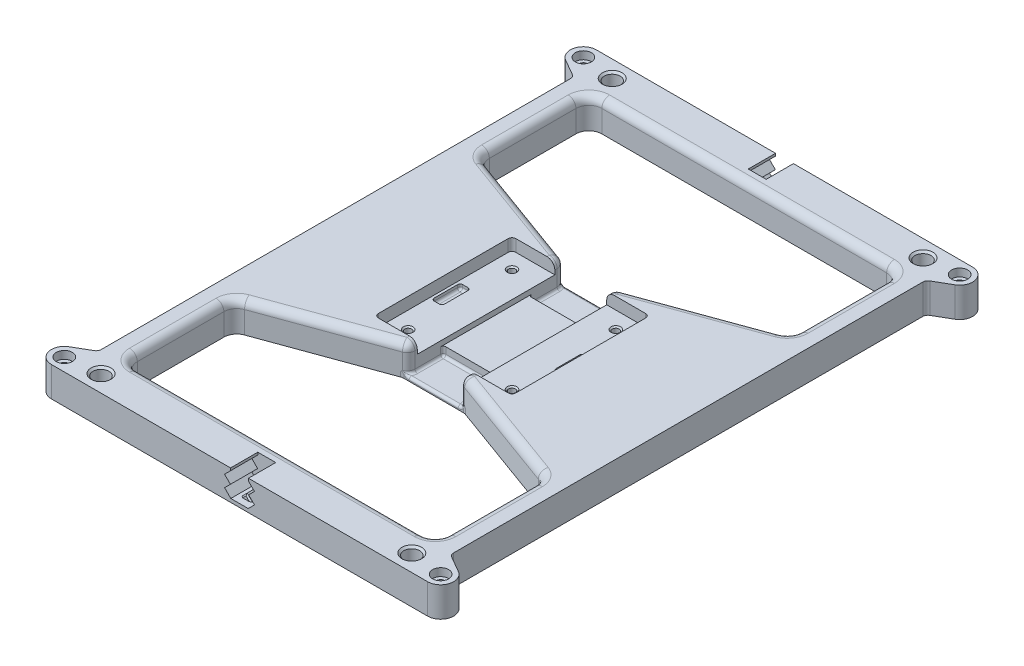
SolidWorks part; units mm, degrees
ref_plane "Front Plane" through (0, 0, 0) normal (0, 0, 1) x (1, 0, 0)
ref_plane "Top Plane" through (0, 0, 0) normal (0, 1, 0) x (1, 0, 0)
ref_plane "Right Plane" through (0, 0, 0) normal (1, 0, 0) x (0, 0, -1)
sketch "Sketch1" plane through (0, 0, 0) normal (0, 1, 0) x (1, 0, 0)
  line L0 (0, 0) -> (0, 90) construction
  line L1 (67.875, 90) -> (-67.875, 90) construction
  line L2 (-67.875, 90) -> (-67.875, 0)
  line L3 (-67.875, 0) -> (67.875, 0)
  line L4 (-67.875, 90) -> (-67.875, 103)
  line L5 (-65.875, 105) -> (65.875, 105)
  line L6 (0, 105) -> (0, 90) construction
  line L7 (67.875, 90) -> (67.875, 103)
  line L8 (67.875, 90) -> (67.875, 0)
  line L14 (-67.875, 93) -> (67.875, 93) construction
  circle A1 centre (-59.875, 98.5) radius 3.075 construction
  circle A2 centre (59.875, 98.5) radius 3.075 construction
  arc A10 (67.875, 103) -> (65.875, 105) centre (65.875, 103) ccw
  arc A11 (-67.875, 103) -> (-65.875, 105) centre (-65.875, 103) cw
  point P42 (67.875, 105)
  point P45 (-67.875, 105)
  dimension "D3" = 6.15
  dimension "D4" = 2
  dimension "D1" = 67.875
  dimension "D2" = 90
  dimension "D6" = 8
  dimension "D7" = 8.5
  dimension "D8" = 12
  dimension "D9" = 3
  dimension "D11" = 105
extrude "Boss-Extrude1" add sketch "Sketch1" along normal blind 11.5
sketch "Sketch3" plane through (0, 11.5, 0) normal (0, 1, 0) x (1, 0, 0)
  line L0 (0, 0) -> (-67.875, 0) construction
  line L2 (0, 0) -> (0, 105) construction
  line L3 (65.875, 105) -> (-65.875, 105) construction
  line L4 (3.96, -16.3) -> (3.96, 16.3)
  line L5 (-2.46, -17.8) -> (2.46, -17.8)
  line L6 (-3.96, 16.3) -> (-3.96, -16.3)
  line L7 (2.46, 17.8) -> (-2.46, 17.8)
  line L8 (0, 17.8) -> (0, -17.8) construction
  arc A0 (-2.46, 17.8) -> (-3.96, 16.3) centre (-2.46, 16.3) ccw
  arc A1 (3.96, 16.3) -> (2.46, 17.8) centre (2.46, 16.3) ccw
  arc A2 (2.46, -17.8) -> (3.96, -16.3) centre (2.46, -16.3) ccw
  arc A3 (-3.96, -16.3) -> (-2.46, -17.8) centre (-2.46, -16.3) ccw
  point P9 (0, 0)
  point P23 (0, 0)
  dimension "D2" = 1.5
  dimension "D1" = 35.6
  dimension "D3" = 7.92
sketch "Sketch4" plane through (0, 11.5, 0) normal (0, 1, 0) x (1, 0, 0)
  circle A2 centre (59.875, 98.5) radius 3.075 construction
  circle A5 centre (-59.875, 98.5) radius 3.075 construction
  circle A10 centre (59.875, 98.5) radius 3.075
  circle A13 centre (-59.875, 98.5) radius 3.075
extrude "Cut-Extrude1" cut sketch "Sketch4" against normal blind 6
sketch "Sketch41" plane through (0, 0, -105) normal (0, 0, -1) x (-1, 0, 0)
  line L0 (5.55, 3.75) -> (3.3, 6) construction
  line L1 (5.55, 3.75) -> (3.3, 1.5) construction
  line L2 (0, 11.5) -> (0, 1.5) construction
  line L3 (0, 1.5) -> (3.3, 1.5) construction
  line L4 (3.3, 6) -> (5.55, 8.25) construction
  line L5 (3.3, 6) -> (3.3, 1.5) construction
  line L6 (5.55, 8.25) -> (3.3, 10.5) construction
  line L7 (3.3, 6) -> (3.3, 10.5) construction
  line L8 (5.55, 3.75) -> (5.55, 8.25) construction
  line L9 (3.3, 10.5) -> (3.3, 11.5) construction
  line L10 (3.3, 1.5) -> (5.55, 1.5) construction
  line L11 (5.55, 1.5) -> (5.55, 3.75) construction
  line L12 (5.55, 3.75) -> (3.3, 3.75) construction
  line L13 (5.55, 8.25) -> (3.3, 8.25) construction
  line L14 (3.3, 6) -> (5.55, 6) construction
  line L15 (-3.3, 11.5) -> (3.3, 11.5)
  line L16 (3.3621, 1.35) -> (-3.3621, 1.35)
  line L17 (0, 1.35) -> (0, 1.5) construction
  line L18 (-3.3, 11.5) -> (-3.45, 11.5)
  line L19 (-3.45, 10.5621) -> (-3.45, 11.5)
  line L20 (3.45, 10.5621) -> (3.45, 11.5)
  line L21 (5.7621, 8.25) -> (3.45, 10.5621)
  line L22 (3.5121, 6) -> (5.7621, 8.25)
  line L23 (5.7621, 3.75) -> (3.5121, 6)
  line L24 (5.7621, 3.75) -> (3.3621, 1.35)
  line L25 (3.3, 11.5) -> (3.45, 11.5)
  line L26 (-5.7621, 8.25) -> (-3.45, 10.5621)
  line L27 (-3.5121, 6) -> (-5.7621, 8.25)
  line L28 (-5.7621, 3.75) -> (-3.5121, 6)
  line L29 (-5.7621, 3.75) -> (-3.3621, 1.35)
  line L30 (-65.875, 11.5) -> (65.875, 11.5) construction
  dimension "D1" = 1
  dimension "D2" = 45
  dimension "D3" = 45
  dimension "D4" = 45
  dimension "D5" = 45
  dimension "D6" = 3.3
  dimension "D7" = 10
  dimension "D8" = 0.15
  dimension "D9" = 0.15
  dimension "D10" = 0.15
  dimension "D11" = 0.15
  dimension "D12" = 0.15
  dimension "D13" = 0.15
extrude "Cut-Extrude31" cut sketch "Sketch41" against normal blind 10.5
sketch "Sketch42" plane through (0, 0, -94.5) normal (0, 0, -1) x (-1, 0, 0)
  line L0 (0, 1.35) -> (0, 3.35) construction
  line L1 (-3.3621, 1.35) -> (3.3621, 1.35) construction
  line L2 (0, 3.35) -> (2, 1.35)
  line L3 (2, 1.35) -> (-2, 1.35)
  line L4 (0, 3.35) -> (-2, 1.35)
  dimension "D1" = 45
  dimension "D2" = 2
extrude "Boss-Extrude9" add sketch "Sketch42" along normal blind 8
chamfer "Chamfer7" distance 0.5 angle 45 2 edges at (1, 2.35, -102.5) (-1, 2.35, -102.5)
mirror "Mirror1" about plane through (-67.875, 11.5, 0) normal (0, 0, -1) of "Boss-Extrude1", "Cut-Extrude1", "Cut-Extrude31", "Boss-Extrude9", "Chamfer7"
sketch "Sketch28" plane through (0, 11.5, 0) normal (0, 1, 0) x (1, 0, 0)
  line L1 (-26, 26) -> (26, 26) construction
  line L2 (-26, 26) -> (-26, -26) construction
  line L3 (-26, -26) -> (26, -26) construction
  line L4 (26, 26) -> (26, -26) construction
  line L5 (-26, 26) -> (26, -26) construction
  line L6 (-26, -26) -> (26, 26) construction
  line L7 (-25, 26.5) -> (25, 26.5)
  line L8 (-26.5, 25) -> (-26.5, -25)
  line L9 (-25, -26.5) -> (25, -26.5)
  line L10 (26.5, 25) -> (26.5, -25)
  line L11 (-26.5, 26.5) -> (26.5, -26.5) construction
  line L12 (-26.5, -26.5) -> (26.5, 26.5) construction
  arc A0 (-25, -26.5) -> (-26.5, -25) centre (-25, -25) cw
  arc A1 (25, -26.5) -> (26.5, -25) centre (25, -25) ccw
  arc A2 (25, 26.5) -> (26.5, 25) centre (25, 25) cw
  arc A3 (-25, 26.5) -> (-26.5, 25) centre (-25, 25) ccw
  point P0 (0, 0)
  point P6 (0, 0)
  dimension "D4" = 1.5
  dimension "D1" = 52
  dimension "D2" = 0.5
  dimension "D3" = 0.5
extrude "Cut-Extrude21" cut sketch "Sketch28" against normal blind 4.6
sketch "Sketch36" plane through (0, 6.9, 0) normal (0, 1, 0) x (1, 0, 0)
  line L2 (-26, 26) -> (-26, -26) construction
  line L3 (-26, 26) -> (26, 26) construction
  circle A0 centre (-20, 20) radius 1.35
  circle A1 centre (20, 20) radius 1.35
  circle A2 centre (20, -20) radius 1.35
  circle A3 centre (-20, -20) radius 1.35
  point P15 (0, 0)
  dimension "D3" = 2.7
  dimension "D1" = 6
  dimension "D2" = 6
  dimension "D4" = 4
extrude "Cut-Extrude28" cut sketch "Sketch36" against normal blind 5
chamfer "Chamfer6" distance 0.5 angle 45 4 edges at (-20, 6.9, 21.35) (20, 6.9, 21.35) (20, 6.9, -18.65) (-20, 6.9, -18.65)
sketch "Sketch29" plane through (0, 6.9, 0) normal (0, 1, 0) x (1, 0, 0)
  line L0 (0, 0) -> (26.5, 0) construction
  line L5 (0, 0) -> (0, -26.5) construction
  line L6 (-25, -26.5) -> (25, -26.5) construction
  line L7 (26.5, -25) -> (26.5, 25) construction
  line L8 (-10, 26.5) -> (10, 16.5) construction
  line L9 (-10, 16.5) -> (10, 26.5) construction
  line L10 (-10, -16.5) -> (10, -16.5)
  line L11 (-10, -16.5) -> (-10, -26.5)
  line L12 (-10, -26.5) -> (10, -26.5)
  line L13 (10, -16.5) -> (10, -26.5)
  line L14 (-10, -16.5) -> (10, -26.5) construction
  line L15 (-10, -26.5) -> (10, -16.5) construction
  line L16 (10, 16.5) -> (10, 26.5)
  line L17 (-10, 26.5) -> (10, 26.5)
  line L18 (-10, 16.5) -> (-10, 26.5)
  line L19 (-10, 16.5) -> (10, 16.5)
  point P4 (0, -21.5)
  point P17 (0, 21.5)
  dimension "D1" = 20
  dimension "D2" = 10
extrude "Cut-Extrude22" cut sketch "Sketch29" against normal blind 5.5
sketch "Sketch25" plane through (0, 0, 0) normal (0, -1, 0) x (1, 0, 0)
  line L0 (0, 0) -> (67.875, 0) construction
  line L1 (67.875, 103) -> (67.875, -103) construction
  line L2 (0, 0) -> (0, 105) construction
  line L4 (75, 95.6699) -> (68.875, 92.1336)
  line L5 (72.5, 100) -> (67.875, 100) construction
  line L6 (67.875, 90.4016) -> (67.875, 103)
  line L8 (65.875, 105) -> (72.5, 105)
  line L9 (-72.5, 100) -> (-67.875, 100) construction
  line L10 (-65.875, 105) -> (-72.5, 105)
  line L11 (-67.875, 90.4016) -> (-67.875, 103)
  line L12 (-75, 95.6699) -> (-68.875, 92.1336)
  line L13 (-72.5, -100) -> (-67.875, -100) construction
  line L14 (72.5, -100) -> (67.875, -100) construction
  line L15 (-75, -95.6699) -> (-68.875, -92.1336)
  line L16 (-67.875, -90.4016) -> (-67.875, -103)
  line L17 (-65.875, -105) -> (-72.5, -105)
  line L18 (65.875, -105) -> (72.5, -105)
  line L19 (67.875, -90.4016) -> (67.875, -103)
  line L20 (75, -95.6699) -> (68.875, -92.1336)
  line L21 (65.875, 105) -> (-65.875, 105) construction
  circle A0 centre (72.5, 100) radius 1.7
  arc A1 (75, 95.6699) -> (72.5, 105) centre (72.5, 100) ccw
  arc A2 (68.875, 92.1336) -> (67.875, 90.4016) centre (69.875, 90.4016) ccw
  arc A17 (67.875, 103) -> (65.875, 105) centre (65.875, 103) ccw
  arc A18 (-67.875, 103) -> (-65.875, 105) centre (-65.875, 103) cw
  arc A19 (-68.875, 92.1336) -> (-67.875, 90.4016) centre (-69.875, 90.4016) cw
  arc A20 (-75, 95.6699) -> (-72.5, 105) centre (-72.5, 100) cw
  circle A21 centre (-72.5, 100) radius 1.7
  circle A22 centre (-72.5, -100) radius 1.7
  arc A23 (-75, -95.6699) -> (-72.5, -105) centre (-72.5, -100) ccw
  arc A24 (-68.875, -92.1336) -> (-67.875, -90.4016) centre (-69.875, -90.4016) ccw
  arc A25 (-67.875, -103) -> (-65.875, -105) centre (-65.875, -103) ccw
  arc A26 (67.875, -103) -> (65.875, -105) centre (65.875, -103) cw
  arc A27 (68.875, -92.1336) -> (67.875, -90.4016) centre (69.875, -90.4016) cw
  arc A28 (75, -95.6699) -> (72.5, -105) centre (72.5, -100) cw
  circle A29 centre (72.5, -100) radius 1.7
  arc A30 (67.875, 103) -> (65.875, 105) centre (65.875, 103) ccw construction
  dimension "D1" = 3.4
  dimension "D2" = 10
  dimension "D6" = 2
  dimension "D3" = 4.625
  dimension "D5" = 60
extrude "Boss-Extrude7" add sketch "Sketch25" against normal up to surface (11.5 mm away) up to face at (0, 11.5, 0)
sketch "Sketch27" plane through (0, 11.5, 0) normal (0, 1, 0) x (1, 0, 0)
  circle A4 centre (-72.5, -100) radius 3.1
  circle A5 centre (72.5, -100) radius 3.1
  circle A6 centre (-72.5, 100) radius 3.1
  circle A7 centre (72.5, 100) radius 3.1
  dimension "D1" = 6.2
extrude "Cut-Extrude20" cut sketch "Sketch27" against normal blind 3
sketch "Sketch37" plane through (0, 6.9, 0) normal (0, 1, 0) x (1, 0, 0)
  line L0 (67.875, 0) -> (0, 0) construction
  line L1 (67.875, -90.4016) -> (67.875, 90.4016) construction
  line L2 (0, 0) -> (-67.875, 0) construction
  line L3 (26.5, -25) -> (26.5, 25) construction
  line L4 (24.5, 5.5) -> (22.5, 5.5)
  line L5 (25.5, 4.5) -> (25.5, -4.5)
  line L6 (24.5, -5.5) -> (22.5, -5.5)
  line L7 (21.5, 4.5) -> (21.5, -4.5)
  line L8 (25.5, 5.5) -> (21.5, -5.5) construction
  line L9 (25.5, -5.5) -> (21.5, 5.5) construction
  line L10 (0, 0) -> (0, 26.5) construction
  line L11 (-10, 16.5) -> (10, 16.5) construction
  line L12 (-24.5, -5.5) -> (-22.5, -5.5)
  line L13 (-25.5, 4.5) -> (-25.5, -4.5)
  line L14 (-24.5, 5.5) -> (-22.5, 5.5)
  line L15 (-21.5, 4.5) -> (-21.5, -4.5)
  line L21 (10, 16.5) -> (10, -16.5)
  line L23 (25, 26.5) -> (-25, 26.5) construction
  line L24 (-10, 16.5) -> (10, 16.5)
  line L25 (-10, 16.5) -> (-10, -16.5)
  line L26 (-10, -16.5) -> (10, -16.5)
  arc A0 (22.5, -5.5) -> (21.5, -4.5) centre (22.5, -4.5) cw
  arc A1 (25.5, -4.5) -> (24.5, -5.5) centre (24.5, -4.5) cw
  arc A2 (22.5, 5.5) -> (21.5, 4.5) centre (22.5, 4.5) ccw
  arc A3 (24.5, 5.5) -> (25.5, 4.5) centre (24.5, 4.5) cw
  arc A4 (-22.5, 5.5) -> (-21.5, 4.5) centre (-22.5, 4.5) cw
  arc A5 (-24.5, 5.5) -> (-25.5, 4.5) centre (-24.5, 4.5) ccw
  arc A6 (-22.5, -5.5) -> (-21.5, -4.5) centre (-22.5, -4.5) ccw
  arc A7 (-25.5, -4.5) -> (-24.5, -5.5) centre (-24.5, -4.5) ccw
  point P5 (23.5, 0)
  point P54 (10, 0)
  point P56 (-10, 0)
  dimension "D4" = 1
  dimension "D1" = 11
  dimension "D2" = 4
  dimension "D3" = 3
extrude "Cut-Extrude29" cut sketch "Sketch37" against normal blind 2
fillet "Fillet20" radius 1 16 edges at (25.2071, 4.9, -5.2071) (25.5, 4.9, 0) (25.2071, 4.9, 5.2071) (23.5, 4.9, 5.5) (21.7929, 4.9, 5.2071) (21.5, 4.9, 0) (21.7929, 4.9, -5.2071) (-21.7929, 4.9, -5.2071) (-21.5, 4.9, 0) (-21.7929, 4.9, 5.2071) (-23.5, 4.9, 5.5) (-25.2071, 4.9, 5.2071) (-25.5, 4.9, 0) (-25.2071, 4.9, -5.2071) (23.5, 4.9, -5.5) (-23.5, 4.9, -5.5)
sketch "Sketch38" plane through (0, 11.5, 0) normal (0, 1, 0) x (1, 0, 0)
  line L0 (11.9739, -30.2185) -> (56.5851, -46.4556)
  line L1 (59.875, -51.1541) -> (59.875, -84.5)
  line L2 (54.875, -89.5) -> (-54.875, -89.5)
  line L3 (0, -89.5) -> (0, -26.5) construction
  line L4 (-10, -26.5) -> (10, -26.5) construction
  line L6 (67.875, -90.4016) -> (67.875, 90.4016) construction
  line L7 (-3.45, -94.5) -> (3.45, -94.5) construction
  line L9 (-25, -26.5) -> (25, -26.5) construction
  line L12 (0, 0) -> (67.875, 0) construction
  line L13 (0, 89.5) -> (0, 26.5) construction
  line L20 (10, -27.3994) -> (10, -26.5)
  line L21 (10, -26.5) -> (25, -26.5) construction
  line L22 (10, -26.5) -> (-10, -26.5)
  line L23 (10, -26.5) -> (10, 26.5) construction
  line L24 (-10, -27.3994) -> (-10, -26.5)
  line L25 (-59.875, -51.1541) -> (-59.875, -84.5)
  line L26 (-11.9739, -30.2185) -> (-56.5851, -46.4556)
  line L27 (-11.9739, 30.2185) -> (-56.5851, 46.4556)
  line L28 (-59.875, 51.1541) -> (-59.875, 84.5)
  line L29 (-10, 27.3994) -> (-10, 26.5)
  line L30 (10, 26.5) -> (-10, 26.5)
  line L31 (10, 27.3994) -> (10, 26.5)
  line L32 (54.875, 89.5) -> (-54.875, 89.5)
  line L33 (59.875, 51.1541) -> (59.875, 84.5)
  line L34 (11.9739, 30.2185) -> (56.5851, 46.4556)
  arc A0 (59.875, -51.1541) -> (56.5851, -46.4556) centre (54.875, -51.1541) ccw
  arc A1 (59.875, -84.5) -> (54.875, -89.5) centre (54.875, -84.5) cw
  arc A8 (11.9739, -30.2185) -> (10, -27.3994) centre (13, -27.3994) cw
  arc A9 (-11.9739, -30.2185) -> (-10, -27.3994) centre (-13, -27.3994) ccw
  arc A10 (-59.875, -84.5) -> (-54.875, -89.5) centre (-54.875, -84.5) ccw
  arc A11 (-59.875, -51.1541) -> (-56.5851, -46.4556) centre (-54.875, -51.1541) cw
  arc A12 (-59.875, 51.1541) -> (-56.5851, 46.4556) centre (-54.875, 51.1541) ccw
  arc A13 (-59.875, 84.5) -> (-54.875, 89.5) centre (-54.875, 84.5) cw
  arc A14 (-11.9739, 30.2185) -> (-10, 27.3994) centre (-13, 27.3994) cw
  arc A15 (11.9739, 30.2185) -> (10, 27.3994) centre (13, 27.3994) ccw
  arc A16 (59.875, 84.5) -> (54.875, 89.5) centre (54.875, 84.5) ccw
  arc A17 (59.875, 51.1541) -> (56.5851, 46.4556) centre (54.875, 51.1541) cw
  point P49 (10, -29.5)
  point P60 (-10, -29.5)
  point P67 (-10, 29.5)
  point P68 (10, 29.5)
  dimension "D4" = 5
  dimension "D6" = 3
  dimension "D1" = 5
  dimension "D2" = 8
  dimension "D3" = 20
  dimension "D5" = 3
extrude "Cut-Extrude30" cut sketch "Sketch38" against normal through all
sketch "Sketch39" plane through (0, 0, 0) normal (0, -1, 0) x (1, 0, 0)
  line L0 (0, 0) -> (67.875, 0) construction
  line L1 (67.875, 90.4016) -> (67.875, -90.4016) construction
  line L2 (-11.9739, 30.2185) -> (11.9739, 30.2185)
  line L3 (10, 27.3994) -> (10, 26.5) construction
  line L4 (10, 26.5) -> (-10, 26.5) construction
  line L5 (-10, 26.5) -> (-10, 27.3994) construction
  line L6 (10, 27.3994) -> (10, 26.5)
  line L7 (10, 26.5) -> (-10, 26.5)
  line L8 (-10, 26.5) -> (-10, 27.3994)
  line L9 (-10, -26.5) -> (-10, -27.3994)
  line L10 (10, -26.5) -> (-10, -26.5)
  line L11 (10, -27.3994) -> (10, -26.5)
  line L12 (-11.9739, -30.2185) -> (11.9739, -30.2185)
  arc A0 (11.9739, 30.2185) -> (10, 27.3994) centre (13, 27.3994) ccw construction
  arc A1 (-10, 27.3994) -> (-11.9739, 30.2185) centre (-13, 27.3994) ccw construction
  arc A2 (11.9739, 30.2185) -> (10, 27.3994) centre (13, 27.3994) ccw
  arc A3 (-10, 27.3994) -> (-11.9739, 30.2185) centre (-13, 27.3994) ccw
  arc A4 (-10, -27.3994) -> (-11.9739, -30.2185) centre (-13, -27.3994) cw
  arc A5 (11.9739, -30.2185) -> (10, -27.3994) centre (13, -27.3994) cw
extrude "Boss-Extrude8" add sketch "Sketch39" against normal up to surface (1.4 mm away) up to face at (0, 1.4, 21.5)
fillet "Fillet21" radius 1 14 edges at (0, 1.4, -16.5) (0, 1.4, 16.5) (-10.5425, 1.4, -29.1201) (10.5425, 1.4, -29.1201) (-10.5425, 1.4, 29.1201) (10.5425, 1.4, 29.1201) (-10, 1.4, -21.9497) (-10, 3.15, -16.5) (10, 1.4, -21.9497) (10, 3.15, -16.5) (-10, 3.15, 16.5) (-10, 1.4, 21.9497) (10, 3.15, 16.5) (10, 1.4, 21.9497)
fillet "Fillet22" radius 3 26 edges at (10, 11.5, -26.9497) (10.5425, 11.5, -29.1201) (34.2795, 11.5, -38.337) (58.9708, 11.5, -48.2862) (59.875, 11.5, -67.827) (58.4105, 11.5, -88.0355) (0, 11.5, -89.5) (-58.4105, 11.5, -88.0355) (-59.875, 11.5, -67.827) (-58.9708, 11.5, -48.2862) (-10, 11.5, -26.9497) (-10.5425, 11.5, -29.1201) (-10, 11.5, 26.9497) (-10.5425, 11.5, 29.1201) (10, 11.5, 26.9497) (10.5425, 11.5, 29.1201) (34.2795, 11.5, 38.337) (58.9708, 11.5, 48.2862) (59.875, 11.5, 67.827) (58.4105, 11.5, 88.0355) (0, 11.5, 89.5) (-58.4105, 11.5, 88.0355) (-59.875, 11.5, 67.827) (-58.9708, 11.5, 48.2862) (-34.2795, 11.5, -38.337) (-34.2795, 11.5, 38.337)
fillet "Fillet24" radius 3 4 edges at (-11.9739, 1.2, 30.2185) (11.9739, 1.2, 30.2185) (11.9739, 1.2, -30.2185) (-11.9739, 1.2, -30.2185)
fillet "Fillet25" radius 1 10 edges at (0, 1.4, 30.2185) (0, 1.4, -30.2185) (-12.1079, 2.1665, -30.2926) (-10.8141, 1.4985, -30.2185) (12.1976, 2.1847, -30.3144) (10.9036, 1.5265, -30.2185) (12.1079, 2.1665, 30.2926) (10.8141, 1.4985, 30.2185) (-12.1976, 2.1847, 30.3144) (-10.9036, 1.5265, 30.2185)
chamfer "Chamfer8" distance 0.75 angle 45 4 edges at (59.875, 11.5, -95.425) (-59.875, 11.5, -95.425) (-59.875, 11.5, 95.425) (59.875, 11.5, 95.425)
equation "\"D3@Sketch28\"=\"D2@Sketch28\""
equation "\"D2@Sketch36\"=\"D1@Sketch36\""
